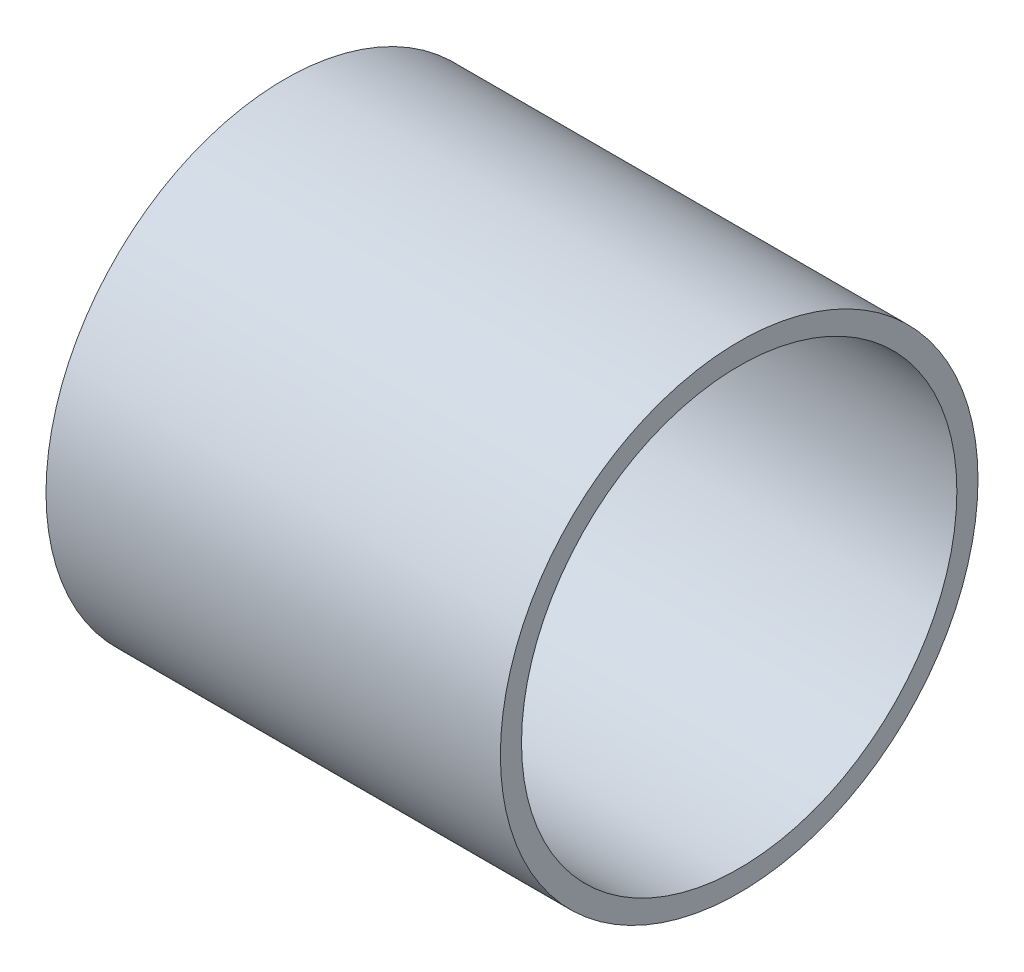
SolidWorks part; units mm, degrees
ref_plane "Vorne" through (0, 0, 0) normal (0, 0, 1) x (1, 0, 0)
ref_plane "Oben" through (0, 0, 0) normal (0, 1, 0) x (1, 0, 0)
ref_plane "Seite" through (0, 0, 0) normal (1, 0, 0) x (0, 0, -1)
sketch "Skizze1" plane through (0, 0, 0) normal (1, 0, 0) x (0, 0, -1)
  circle A0 centre (0, 0) radius 5.15
  circle A1 centre (0, 0) radius 5.65
  dimension "D1" = 10.3
  dimension "D2" = 11.3
extrude "Aufsatz-Linear austragen1" add sketch "Skizze1" along normal blind 10.75
